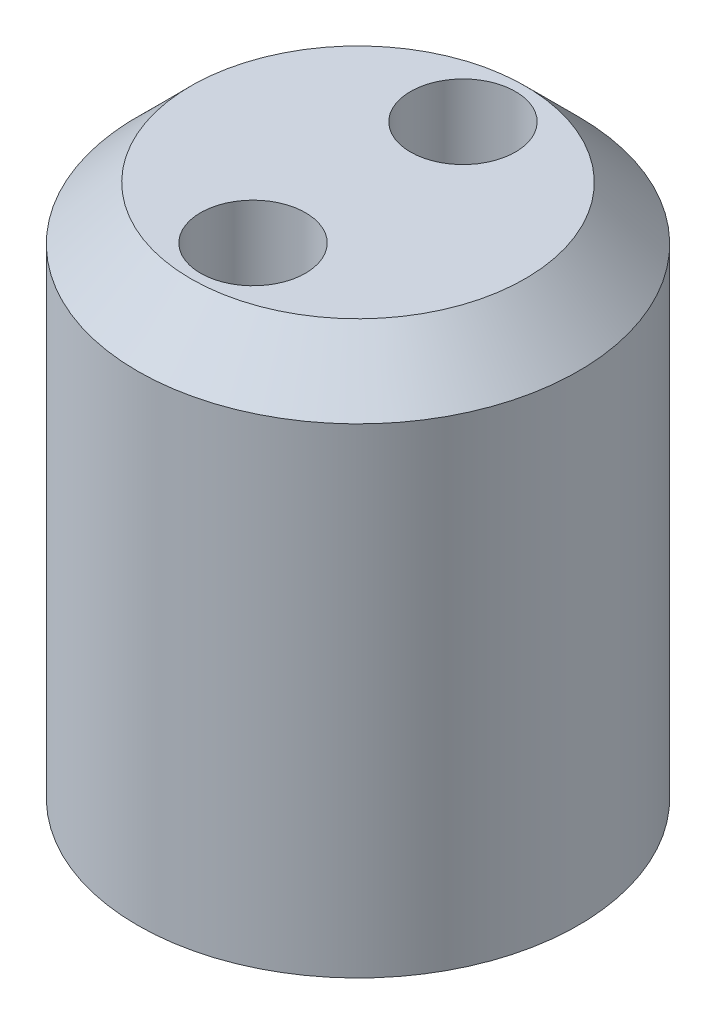
SolidWorks part; units mm, degrees
ref_plane "Front Plane" through (0, 0, 0) normal (0, 0, 1) x (1, 0, 0)
ref_plane "Top Plane" through (0, 0, 0) normal (0, 1, 0) x (1, 0, 0)
ref_plane "Right Plane" through (0, 0, 0) normal (1, 0, 0) x (0, 0, -1)
sketch "Sketch1" plane through (0, 0, 0) normal (0, 1, 0) x (1, 0, 0)
  line L0 (0, -5) -> (0, 5) construction
  circle A0 centre (0, 0) radius 10.5
  circle A2 centre (0, 5) radius 2.5
  circle A3 centre (0, -5) radius 2.5
  dimension "D1" = 21
  dimension "D2" = 5
  dimension "D3" = 10
extrude "Boss-Extrude1" add sketch "Sketch1" along normal blind 25.4
chamfer "Chamfer1" distance 2.54 angle 45 1 edges at (0, 25.4, 10.5)
equation "\"cf_tube_outer_diameter\"= 25mm"
equation "\"cf_tube_inner_diameter\"= 21mm"
equation "\"mid_plate_mid_to_top\"= 100mm"
equation "\"mid_plate_mid_to_bottom\"= 30mm"
equation "\"mid_plate_horizontal_spacing\"= 250mm"
equation "\"cf_plate_thickness\"= 3mm"
equation "\"mid_tube_length\"= 500mm"
equation "\"D1@Sketch1\"=\"cf_tube_inner_diameter\""
